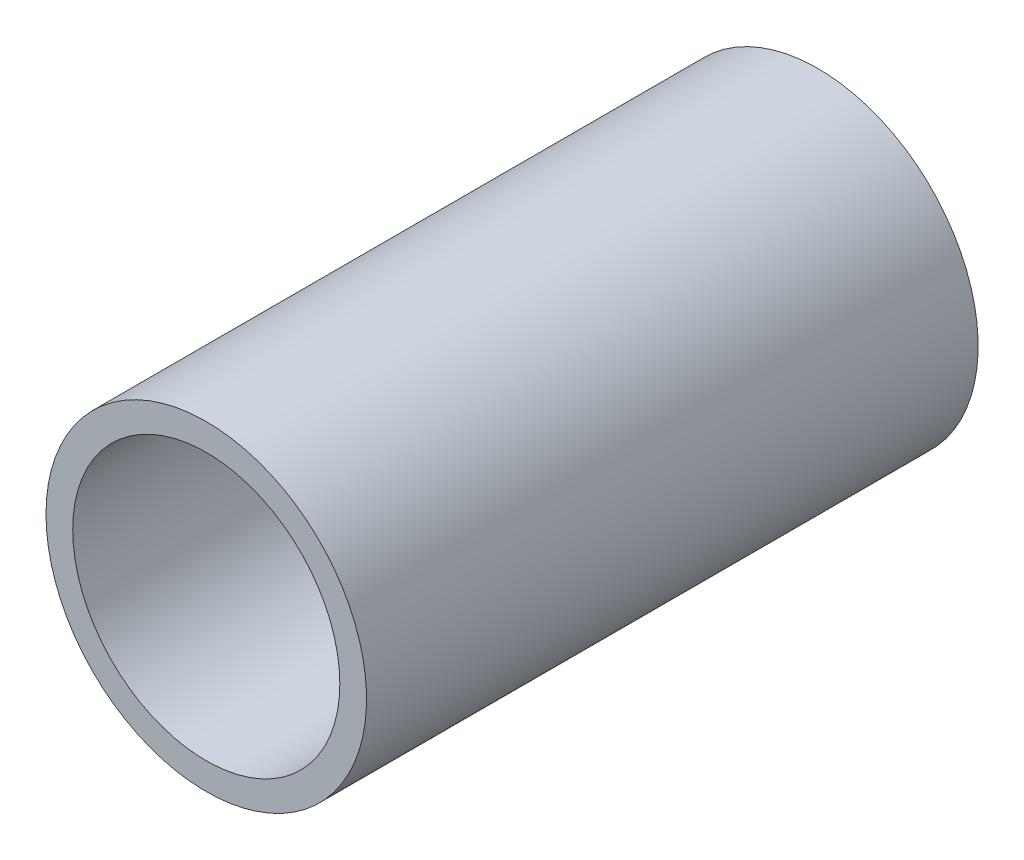
SolidWorks part; units mm, degrees
material "PLA 50%"
ref_plane "Front Plane" through (0, 0, 0) normal (0, 0, 1) x (1, 0, 0)
ref_plane "Top Plane" through (0, 0, 0) normal (0, 1, 0) x (1, 0, 0)
ref_plane "Right Plane" through (0, 0, 0) normal (1, 0, 0) x (0, 0, -1)
ref_axis "X" through (-88.99, 0, 0) along (1, 0, 0)
ref_axis "Y" through (0, 55, 0) along (0, -1, 0)
ref_axis "Z" through (0, 0, -88.99) along (0, 0, 1)
sketch "Sketch1" plane through (0, 0, 0) normal (0, 0, 1) x (1, 0, 0)
  circle A0 centre (0, 0) radius 5
  circle A1 centre (0, 0) radius 6
  dimension "D1" = 10
  dimension "D2" = 12
extrude "Boss-Extrude1" add sketch "Sketch1" along normal up to surface (22.897 mm away)
